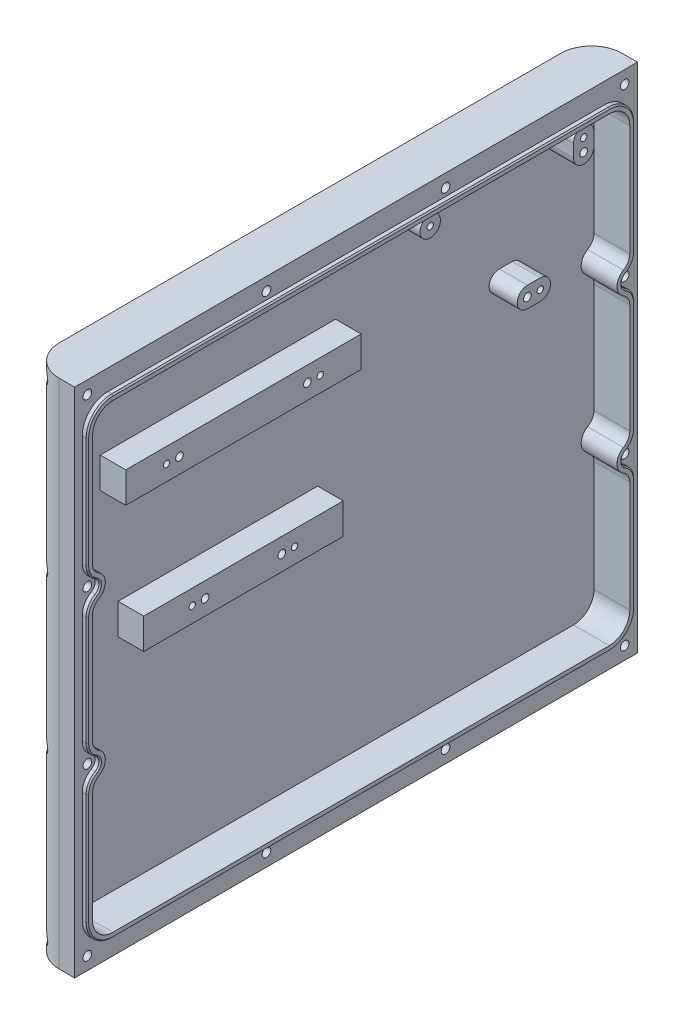
SolidWorks part; units mm, degrees
material "6061 Alloy"
ref_plane "Front Plane" through (0, 0, 0) normal (0, 0, 1) x (1, 0, 0)
ref_plane "Top Plane" through (0, 0, 0) normal (0, 1, 0) x (1, 0, 0)
ref_plane "Right Plane" through (0, 0, 0) normal (1, 0, 0) x (0, 0, -1)
sketch "Sketch1" plane through (0, 0, 0) normal (1, 0, 0) x (0, 0, -1)
  line L0 (-105, 25) -> (-105, -25)
  line L1 (-110, 100) -> (110, 100)
  line L2 (-110, 100) -> (-110, -100)
  line L3 (-110, -100) -> (110, -100)
  line L4 (110, 100) -> (110, -100)
  line L5 (-105, -35) -> (-105, -90)
  line L6 (105, 25) -> (105, -25)
  line L7 (-105, 90) -> (105, 90)
  line L8 (-105, 90) -> (-105, 35)
  line L9 (-105, -90) -> (105, -90)
  line L10 (105, 90) -> (105, 35)
  line L11 (105, -35) -> (105, -90)
  arc A0 (-105, 25) -> (-105, 35) centre (-105, 30) ccw
  arc A1 (-105, -35) -> (-105, -25) centre (-105, -30) ccw
  arc A2 (105, 35) -> (105, 25) centre (105, 30) ccw
  arc A3 (105, -25) -> (105, -35) centre (105, -30) ccw
  point P0 (0, 0)
  point P6 (0, 0)
  dimension "D10" = 60
  dimension "D11" = 10
  dimension "D1" = 220
  dimension "D2" = 200
  dimension "D3" = 210
  dimension "D4" = 180
  dimension "D5" = 90
  dimension "D6" = 100
  dimension "D7" = 105
  dimension "D8" = 110
  dimension "D9" = 60
extrude "Boss-Extrude1" add sketch "Sketch1" along normal blind 6 contours L2 L3 L4 L1
extrude "Boss-Extrude2" add sketch "Sketch1<3>" along normal blind 18
sketch "Sketch1<3>" plane through (0, 0, 0) normal (1, 0, 0) x (0, 0, -1) same geometry as "Sketch1"
sketch "Sketch2" plane through (6, 0, 0) normal (1, 0, 0) x (0, 0, -1)
  line L0 (90, 84) -> (90, 79) construction
  line L1 (94, 84) -> (94, 79)
  line L2 (86, 84) -> (86, 79)
  line L3 (68, 41) -> (73, 41) construction
  line L6 (105, 90) -> (-105, 90) construction
  line L7 (105, 35) -> (105, 90) construction
  line L8 (68, 45) -> (73, 45)
  line L9 (68, 37) -> (73, 37)
  arc A0 (94, 84) -> (86, 84) centre (90, 84) ccw
  arc A1 (86, 79) -> (94, 79) centre (90, 79) ccw
  circle A2 centre (30, 84) radius 4
  arc A5 (68, 45) -> (68, 37) centre (68, 41) ccw
  arc A6 (73, 37) -> (73, 45) centre (73, 41) ccw
  point P2 (90, 81.5)
  point P11 (70.5, 41)
  dimension "D4" = 4
  dimension "D6" = 8
  dimension "D10" = 4
  dimension "D1" = 6
  dimension "D2" = 60
  dimension "D3" = 5
  dimension "D5" = 15
  dimension "D7" = 43
  dimension "D8" = 17
  dimension "D9" = 5
extrude "Boss-Extrude3" add sketch "Sketch2" along normal blind 11
sketch "Sketch3" plane through (17, 0, 0) normal (1, 0, 0) x (0, 0, -1)
  circle A0 centre (30, 84) radius 1.2295
  circle A1 centre (90, 84) radius 1.2295
  circle A2 centre (73, 41) radius 1.2295
  dimension "D1" = 2.459
extrude "Cut-Extrude1" cut sketch "Sketch3" against normal blind 7
hole_wizard "Ø3.0mm Dowel Hole1" positions "Sketch4" profile "Sketch5" hole size "Ø3.0" standard "ANSI Metric"
sketch "Sketch4" plane through (17, 0, 0) normal (1, 0, 0) x (0, 0, -1)
  point P0 (68, 41)
  point P3 (90, 79)
sketch "Sketch5" plane through (17, 41, -68) normal (0, 1, 0) x (0, 0, -1)
  line L0 (0, 0) -> (0, 5.9013)
  line L1 (0, 5.9013) -> (1.5, 5)
  line L2 (1.5, 5) -> (1.5, 0)
  line L5 (1.5, 0) -> (0, 0)
  line L10 (0, 5.9013) -> (-1.5, 5) construction
  line L11 (0, -6.35) -> (0, 107.95) construction
  dimension "Hole Dia." = 3
  dimension "Hole Depth" = 5
  dimension "Drill Angle" = 118
sketch "Sketch6" plane through (6, 0, 0) normal (1, 0, 0) x (0, 0, -1)
  line L0 (-42, 84.1007) -> (-42, -37.9382) construction
  line L1 (-88, 60) -> (4, 60)
  line L2 (-88, 60) -> (-88, 48)
  line L3 (-88, 48) -> (4, 48)
  line L4 (4, 60) -> (4, 48)
  line L5 (-81, 7) -> (-3, 7)
  line L6 (-81, 7) -> (-81, -5)
  line L7 (-81, -5) -> (-3, -5)
  line L8 (-3, 7) -> (-3, -5)
  line L9 (-105, 90) -> (-105, 35) construction
  line L10 (105, 90) -> (-105, 90) construction
  dimension "D1" = 63
  dimension "D2" = 12
  dimension "D3" = 12
  dimension "D4" = 30
  dimension "D5" = 41
  dimension "D6" = 78
  dimension "D7" = 92
extrude "Boss-Extrude4" add sketch "Sketch6" along normal blind 10
sketch "Sketch7" plane through (16, 0, 0) normal (1, 0, 0) x (0, 0, -1)
  line L0 (-42, 60) -> (-42, -5) construction
  line L1 (4, 60) -> (-88, 60) construction
  line L2 (-81, -5) -> (-3, -5) construction
  line L3 (-3, 7) -> (-81, 7) construction
  circle A0 centre (-72, 54) radius 1.2295
  circle A1 centre (-12, 54) radius 1.2295
  circle A2 centre (-62, 1) radius 1.2295
  circle A3 centre (-22, 1) radius 1.2295
  point P14 (0, 0)
  point P15 (0, 0)
  dimension "D1" = 30
  dimension "D2" = 2.459
  dimension "D7" = 6
  dimension "D3" = 30
  dimension "D4" = 6
  dimension "D5" = 20
  dimension "D6" = 20
extrude "Cut-Extrude2" cut sketch "Sketch7" against normal blind 7
hole_wizard "Ø3.0mm Dowel Hole2" positions "Sketch9" profile "Sketch10" hole size "Ø3.0" standard "ANSI Metric"
sketch "Sketch9" plane through (16, 0, 0) normal (1, 0, 0) x (0, 0, -1)
  line L0 (4, 60) -> (-88, 60) construction
  line L1 (-3, 7) -> (-81, 7) construction
  circle A0 centre (-72, 54) radius 1.2295 construction
  circle A1 centre (-12, 54) radius 1.2295 construction
  circle A2 centre (-62, 1) radius 1.2295 construction
  circle A3 centre (-22, 1) radius 1.2295 construction
  point P0 (-67, 54)
  point P2 (-17, 54)
  point P4 (-57, 1)
  point P6 (-27, 1)
  point P9 (0, 0)
  point P20 (0, 0)
  dimension "D2" = 5
  dimension "D4" = 5
  dimension "D1" = 6
  dimension "D3" = 5
  dimension "D5" = 5
  dimension "D6" = 6
sketch "Sketch10" plane through (16, 54, 67) normal (0, 1, 0) x (0, 0, -1)
  line L0 (0, 0) -> (0, 4.9013)
  line L1 (0, 4.9013) -> (1.5, 4)
  line L2 (1.5, 4) -> (1.5, 0)
  line L5 (1.5, 0) -> (0, 0)
  line L10 (0, 4.9013) -> (-1.5, 4) construction
  line L11 (0, -6.35) -> (0, 107.95) construction
  dimension "Hole Dia." = 3
  dimension "Hole Depth" = 4
  dimension "Drill Angle" = 118
fillet "Fillet1" radius 8 4 edges at (12, -90, 105) (12, 90, 105) (12, -90, -105) (12, 90, -105)
fillet "Fillet2" radius 5 8 edges at (12, -25, -105) (12, -35, -105) (12, 25, -105) (12, 35, -105) (12, -35, 105) (12, -25, 105) (12, 25, 105) (12, 35, 105)
sketch "Sketch11" plane through (18, 0, 0) normal (1, 0, 0) x (0, 0, -1)
  line L0 (107, -82) -> (107, -38.6603)
  line L1 (-97, -92) -> (97, -92)
  line L2 (-107, -38.6603) -> (-107, -82)
  line L3 (-107, 21.3397) -> (-107, -21.3397)
  line L4 (-107, 82) -> (-107, 38.6603)
  line L5 (97, 92) -> (-97, 92)
  line L6 (107, 38.6603) -> (107, 82)
  line L7 (107, -21.3397) -> (107, 21.3397)
  line L8 (105, -21.3397) -> (105, 21.3397)
  line L9 (105, 38.6603) -> (105, 82)
  line L10 (97, 90) -> (-97, 90)
  line L11 (-105, 82) -> (-105, 38.6603)
  line L12 (-105, 21.3397) -> (-105, -21.3397)
  line L13 (-105, -38.6603) -> (-105, -82)
  line L14 (-97, -90) -> (97, -90)
  line L15 (105, -82) -> (105, -38.6603)
  line L16 (105, -21.3397) -> (105, 21.3397)
  line L17 (105, 38.6603) -> (105, 82)
  line L18 (97, 90) -> (-97, 90)
  line L19 (-105, 82) -> (-105, 38.6603)
  line L20 (-105, 21.3397) -> (-105, -21.3397)
  line L21 (-105, -38.6603) -> (-105, -82)
  line L22 (-97, -90) -> (97, -90)
  line L23 (105, -82) -> (105, -38.6603)
  arc A0 (103.5, -27.4019) -> (103.5, -32.5981) centre (105, -30) ccw
  arc A1 (107, -38.6603) -> (103.5, -32.5981) centre (100, -38.6603) ccw
  arc A2 (97, -92) -> (107, -82) centre (97, -82) ccw
  arc A3 (-107, -82) -> (-97, -92) centre (-97, -82) ccw
  arc A4 (-103.5, -32.5981) -> (-107, -38.6603) centre (-100, -38.6603) ccw
  arc A5 (-103.5, -32.5981) -> (-103.5, -27.4019) centre (-105, -30) ccw
  arc A6 (-107, -21.3397) -> (-103.5, -27.4019) centre (-100, -21.3397) ccw
  arc A7 (-103.5, 27.4019) -> (-107, 21.3397) centre (-100, 21.3397) ccw
  arc A8 (-103.5, 27.4019) -> (-103.5, 32.5981) centre (-105, 30) ccw
  arc A9 (-107, 38.6603) -> (-103.5, 32.5981) centre (-100, 38.6603) ccw
  arc A10 (-97, 92) -> (-107, 82) centre (-97, 82) ccw
  arc A11 (107, 82) -> (97, 92) centre (97, 82) ccw
  arc A12 (103.5, 32.5981) -> (107, 38.6603) centre (100, 38.6603) ccw
  arc A13 (103.5, 32.5981) -> (103.5, 27.4019) centre (105, 30) ccw
  arc A14 (107, 21.3397) -> (103.5, 27.4019) centre (100, 21.3397) ccw
  arc A15 (103.5, -27.4019) -> (107, -21.3397) centre (100, -21.3397) ccw
  arc A16 (102.5, -25.6699) -> (102.5, -34.3301) centre (105, -30) ccw
  arc A17 (102.5, -25.6699) -> (105, -21.3397) centre (100, -21.3397) ccw
  arc A18 (105, 21.3397) -> (102.5, 25.6699) centre (100, 21.3397) ccw
  arc A19 (102.5, 34.3301) -> (102.5, 25.6699) centre (105, 30) ccw
  arc A20 (102.5, 34.3301) -> (105, 38.6603) centre (100, 38.6603) ccw
  arc A21 (105, 82) -> (97, 90) centre (97, 82) ccw
  arc A22 (-97, 90) -> (-105, 82) centre (-97, 82) ccw
  arc A23 (-105, 38.6603) -> (-102.5, 34.3301) centre (-100, 38.6603) ccw
  arc A24 (-102.5, 25.6699) -> (-102.5, 34.3301) centre (-105, 30) ccw
  arc A25 (-102.5, 25.6699) -> (-105, 21.3397) centre (-100, 21.3397) ccw
  arc A26 (-105, -21.3397) -> (-102.5, -25.6699) centre (-100, -21.3397) ccw
  arc A27 (-102.5, -34.3301) -> (-102.5, -25.6699) centre (-105, -30) ccw
  arc A28 (-102.5, -34.3301) -> (-105, -38.6603) centre (-100, -38.6603) ccw
  arc A29 (-105, -82) -> (-97, -90) centre (-97, -82) ccw
  arc A30 (97, -90) -> (105, -82) centre (97, -82) ccw
  arc A31 (105, -38.6603) -> (102.5, -34.3301) centre (100, -38.6603) ccw
  arc A32 (102.5, -25.6699) -> (102.5, -34.3301) centre (105, -30) ccw
  arc A33 (102.5, -25.6699) -> (105, -21.3397) centre (100, -21.3397) ccw
  arc A34 (105, 21.3397) -> (102.5, 25.6699) centre (100, 21.3397) ccw
  arc A35 (102.5, 34.3301) -> (102.5, 25.6699) centre (105, 30) ccw
  arc A36 (102.5, 34.3301) -> (105, 38.6603) centre (100, 38.6603) ccw
  arc A37 (105, 82) -> (97, 90) centre (97, 82) ccw
  arc A38 (-97, 90) -> (-105, 82) centre (-97, 82) ccw
  arc A39 (-105, 38.6603) -> (-102.5, 34.3301) centre (-100, 38.6603) ccw
  arc A40 (-102.5, 25.6699) -> (-102.5, 34.3301) centre (-105, 30) ccw
  arc A41 (-102.5, 25.6699) -> (-105, 21.3397) centre (-100, 21.3397) ccw
  arc A42 (-105, -21.3397) -> (-102.5, -25.6699) centre (-100, -21.3397) ccw
  arc A43 (-102.5, -34.3301) -> (-102.5, -25.6699) centre (-105, -30) ccw
  arc A44 (-102.5, -34.3301) -> (-105, -38.6603) centre (-100, -38.6603) ccw
  arc A45 (-105, -82) -> (-97, -90) centre (-97, -82) ccw
  arc A46 (97, -90) -> (105, -82) centre (97, -82) ccw
  arc A47 (105, -38.6603) -> (102.5, -34.3301) centre (100, -38.6603) ccw
  dimension "D1" = 0
  dimension "D2" = 2
extrude "Boss-Extrude5" add sketch "Sketch11" along normal blind 2
chamfer "Chamfer1" distance 0.5 angle 45 24 edges at (20, -60.3301, -107) (20, -35.1603, -106.0622) (20, -89.0711, -104.0711) (20, -30, -102) (20, -92, 0) (20, -24.8397, -106.0622) (20, -89.0711, 104.0711) (20, 0, -107) (20, -60.3301, 107) (20, 24.8397, -106.0622) (20, -35.1603, 106.0622) (20, 30, -102) (20, -30, 102) (20, 35.1603, -106.0622) (20, -24.8397, 106.0622) (20, 60.3301, -107) (20, 0, 107) (20, 89.0711, -104.0711) (20, 24.8397, 106.0622) (20, 92, 0) (20, 30, 102) (20, 89.0711, 104.0711) (20, 35.1603, 106.0622) (20, 60.3301, 107)
sketch "Sketch12" plane through (18, 0, 0) normal (1, 0, 0) x (0, 0, -1)
  line L0 (110, 100) -> (-110, 100) construction
  line L2 (-110, -100) -> (110, -100) construction
  circle A0 centre (-105, 95) radius 1.7
  circle A1 centre (-105, 30) radius 1.7
  circle A2 centre (-105, -30) radius 1.7
  circle A3 centre (-105, -95) radius 1.7
  circle A4 centre (-35, -95) radius 1.7
  circle A5 centre (35, -95) radius 1.7
  circle A6 centre (105, -95) radius 1.7
  circle A7 centre (105, -30) radius 1.7
  circle A8 centre (105, 30) radius 1.7
  circle A9 centre (105, 95) radius 1.7
  circle A10 centre (-35, 95) radius 1.7
  circle A11 centre (35, 95) radius 1.7
  point P28 (0, 0)
  point P31 (0, 0)
  point P32 (0, 0)
  point P33 (0, 0)
  point P34 (0, 0)
  point P35 (0, 0)
  point P38 (0, 0)
  dimension "D2" = 3.4
  dimension "D3" = 5
  dimension "D1" = 5
  dimension "D4" = 70
  dimension "D5" = 70
extrude "Cut-Extrude3" cut sketch "Sketch12" against normal up to surface (18 mm away) up to face at (0, 0, 0)
sketch "Sketch13" plane through (0, 0, 0) normal (-1, 0, 0) x (0, 0, 1)
  circle A0 centre (-105, 95) radius 3.25
  circle A1 centre (-35, 95) radius 3.25
  circle A2 centre (35, 95) radius 3.25
  circle A3 centre (105, 95) radius 3.25
  circle A4 centre (105, 30) radius 3.25
  circle A5 centre (105, -30) radius 3.25
  circle A6 centre (105, -95) radius 3.25
  circle A7 centre (35, -95) radius 3.25
  circle A8 centre (-35, -95) radius 3.25
  circle A9 centre (-105, -95) radius 3.25
  circle A10 centre (-105, -30) radius 3.25
  circle A11 centre (-105, 30) radius 3.25
  dimension "D1" = 6.5
extrude "Cut-Extrude4" cut sketch "Sketch13" against normal blind 12
fillet "Fillet3" radius 12 2 edges at (0, 0, -110) (0, 0, 110)
